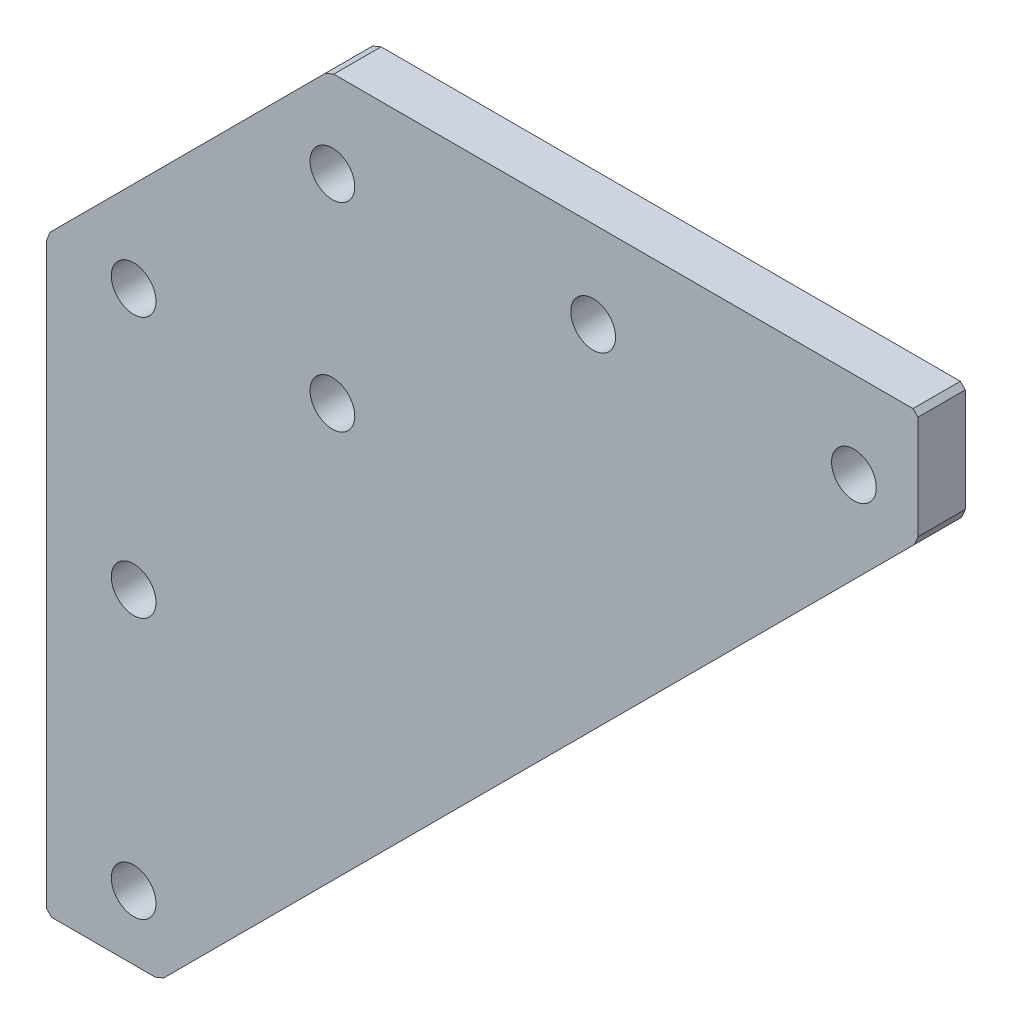
SolidWorks part; units mm, degrees
material "6061-T6 (SS)"
ref_plane "Front Plane" through (0, 0, 0) normal (0, 0, 1) x (1, 0, 0)
ref_plane "Top Plane" through (0, 0, 0) normal (0, 1, 0) x (1, 0, 0)
ref_plane "Right Plane" through (0, 0, 0) normal (1, 0, 0) x (0, 0, -1)
sketch "Sketch1" plane through (0, 0, 0) normal (0, 0, 1) x (1, 0, 0)
  line L1 (-17.5, -157.849) -> (5.3401, -157.849)
  line L2 (5.3401, -157.849) -> (157.849, -5.3401)
  line L3 (157.849, -5.3401) -> (157.849, 17.5)
  line L4 (157.849, 17.5) -> (39.2678, 17.5)
  line L6 (144.9569, 0) -> (157.849, 0) construction
  line L9 (0, -144.9569) -> (0, -157.849) construction
  line L10 (0, -40) -> (40, -40) construction
  line L11 (0, 0) -> (40, 0) construction
  line L12 (40, 0) -> (40, -40) construction
  line L13 (144.9569, 0) -> (40, 0) construction
  line L14 (0, 0) -> (0, -40) construction
  line L15 (0, -40) -> (0, -144.9569) construction
  line L16 (-17.5, -39.2678) -> (-17.5, -157.849)
  line L17 (-17.5, -39.2678) -> (39.2678, 17.5)
  line L18 (0, -40) -> (-9.1161, -30.8839) construction
  line L19 (0, -20) -> (20, 0) construction
  line L20 (144.9569, 0) -> (154.073, -9.1161) construction
  dimension "D1" = 40
  dimension "D2" = 104.9569
  dimension "D3" = 100
  dimension "D4" = 17.5
  dimension "D5" = 2.5
extrude "Boss-Extrude1" add sketch "Sketch1" along normal mid plane 9.525
hole_wizard "M8 Clearance Hole1" positions "Sketch2" profile "Sketch3" hole size "M8" standard "ANSI Metric" end condition up to next
sketch "Sketch2" plane through (0, 0, 4.7625) normal (0, 0, 1) x (1, 0, 0)
  line L2 (144.9569, 0) -> (40, 0) construction
  line L3 (0, -40) -> (0, -144.9569) construction
  point P0 (0, -92.4784)
  point P3 (144.9569, 0)
  point P6 (92.4784, 0)
  point P10 (0, -40)
  point P14 (0, -144.9569)
  point P17 (40, 0)
  point P36 (40, -40)
sketch "Sketch3" plane through (0, -92.4784, 4.7625) normal (1, 0, 0) x (0, -1, 0)
  line L0 (0, 0) -> (0, 9.525)
  line L1 (0, 9.525) -> (4.5, 9.525)
  line L2 (4.5, 9.525) -> (4.5, 0)
  line L5 (4.5, 0) -> (0, 0)
  line L11 (0, -6.35) -> (0, 107.95) construction
  dimension "Thru Hole Dia." = 9
  dimension "Thru Hole Depth" = 9.525
chamfer "Chamfer1" distance 1 distance2 1 6 edges at (157.849, 17.5, 0) (-17.5, -157.849, 0) (157.849, -5.3401, 0) (5.3401, -157.849, 0) (-17.5, -39.2678, 0) (39.2678, 17.5, 0) tangent propagation no
